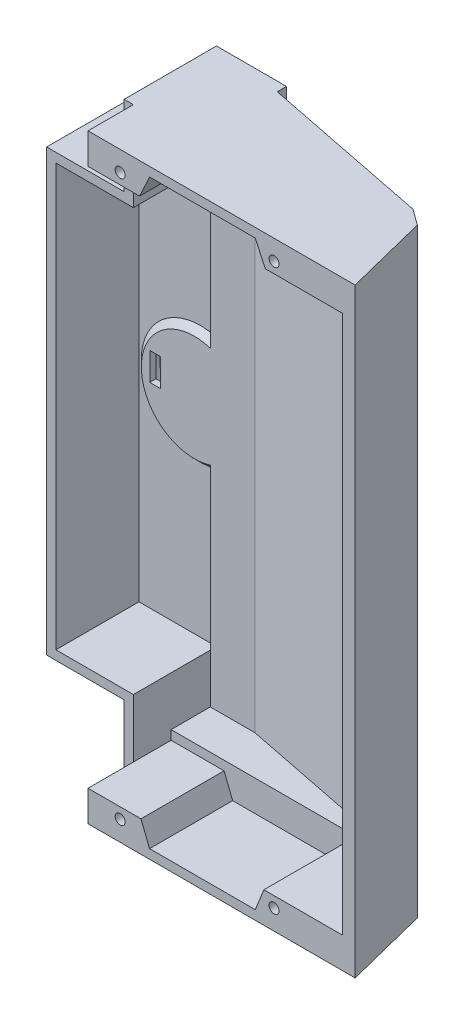
SolidWorks part; units mm, degrees
ref_plane "Alzado" through (0, 0, 0) normal (0, 0, 1) x (1, 0, 0)
ref_plane "Planta" through (0, 0, 0) normal (0, 1, 0) x (1, 0, 0)
ref_plane "Vista lateral" through (0, 0, 0) normal (1, 0, 0) x (0, 0, -1)
sketch "Croquis1" plane through (0, 0, 0) normal (0, 1, 0) x (1, 0, 0)
  line L1 (-39.29, 8.87) -> (39.29, 8.87)
  line L2 (-39.29, 8.87) -> (-39.29, -8.87)
  line L3 (-39.29, -8.87) -> (39.29, -8.87)
  line L4 (39.29, 8.87) -> (39.29, -8.87)
  line L5 (-39.29, 8.87) -> (39.29, -8.87) construction
  line L6 (-39.29, -8.87) -> (39.29, 8.87) construction
  point P0 (0, 0)
  dimension "D1" = 17.74
  dimension "D2" = 78.58
extrude "Saliente-Extruir1" add sketch "Croquis1" along normal blind 195
sketch "Croquis2" plane through (0, 0, 0) normal (0, -1, 0) x (1, 0, 0)
  line L2 (-39.29, 8.87) -> (39.29, 8.87) construction
  line L3 (39.29, 8.87) -> (39.29, -8.87) construction
  line L7 (39.29, 5.87) -> (-19.5325, -5.87)
  line L9 (39.29, -8.87) -> (-39.29, -8.87) construction
  line L10 (-19.5325, -5.87) -> (-19.5325, -8.87)
  line L11 (-19.5325, -8.87) -> (39.29, -8.87)
  line L12 (39.29, -8.87) -> (39.29, 5.87)
  line M3 (39.29, -8.87) -> (39.29, 8.87)
  line M6 (-39.29, -8.87) -> (39.29, -8.87)
  dimension "D1" = 3
  dimension "D2" = 3
extrude "Cortar-Extruir1" cut sketch "Croquis2" against normal through all both and the other way through all contours L7 M3 M6 region at (16.3667, 0, -3.7876)
chamfer "Chaflán1" distance 3 angle 45 1 edges at (39.29, 97.5, 5.87) first distance on face at (39.29, 97.5, 7.37)
sketch "Croquis4" plane through (0, 0, -8.87) normal (0, 0, -1) x (-1, 0, 0)
  line L1 (39.29, 195) -> (42.29, 195)
  line L2 (39.29, 195) -> (39.29, 0)
  line L3 (39.29, 0) -> (42.29, 0)
  line L4 (42.29, 195) -> (42.29, 0)
  dimension "D1" = 3
extrude "Saliente-Extruir2" add sketch "Croquis4" against normal blind 3
sketch "Croquis5" plane through (0, 0, -8.87) normal (0, 0, -1) x (-1, 0, 0)
  line L0 (42.29, 0) -> (42.29, 195) construction
  line L1 (42.29, 26) -> (67.47, 26)
  line L2 (42.29, 26) -> (42.29, 169)
  line L3 (42.29, 169) -> (67.47, 169)
  line L4 (67.47, 26) -> (67.47, 169)
  dimension "D1" = 26
  dimension "D2" = 143
  dimension "D3" = 25.18
extrude "Saliente-Extruir3" add sketch "Croquis5" against normal blind 3
fillet "Redondeo1" radius 2 1 edges at (-67.47, 97.5, -8.87)
sketch "Croquis6" plane through (0, 0, 8.87) normal (0, 0, 1) x (1, 0, 0)
  line L0 (-39.29, 195) -> (-39.29, 0) construction
  line L1 (-39.29, 195) -> (39.29, 195) construction
  line L2 (39.29, 97.5) -> (-154.1795, 97.5) construction
  line L3 (39.29, 195) -> (39.29, 0) construction
  circle A0 centre (-28.84, 188.5) radius 1.625
  circle A1 centre (21.16, 188.5) radius 1.625
  circle A2 centre (21.16, 6.5) radius 1.625
  circle A3 centre (-28.84, 6.5) radius 1.625
  dimension "D2" = 50
  dimension "D3" = 6.5
  dimension "D4" = 3.25
  dimension "D1" = 10.45
extrude "Cortar-Extruir2" cut sketch "Croquis6" against normal through all both and the other way through all
sketch "Croquis7" plane through (0, 0, 8.87) normal (0, 0, 1) x (1, 0, 0)
  circle A0 centre (-28.84, 188.5) radius 3.5
  circle A1 centre (21.16, 188.5) radius 3.5
  circle A2 centre (-28.84, 6.5) radius 3.5
  circle A3 centre (21.16, 6.5) radius 3.5
  dimension "D1" = 7
extrude "Cortar-Extruir3" cut sketch "Croquis7" against normal through all from offset 3 offset against normal yes
sketch "Croquis8" plane through (0, 0, -8.87) normal (0, 0, -1) x (-1, 0, 0)
  line L0 (65.47, 26) -> (65.47, 169) construction
  circle A0 centre (44.4699, 97.5) radius 16.25
  circle A1 centre (44.4699, 97.5) radius 8.75
  point P6 (65.47, 97.5)
  dimension "D1" = 32.5
  dimension "D2" = 17.5
extrude "Cortar-Extruir4" cut sketch "Croquis8" against normal blind 3
sketch "Croquis9" plane through (0, 0, -5.87) normal (0, 0, 1) x (1, 0, 0)
  circle A0 centre (-44.4699, 97.5) radius 17.25
  arc A1 (-39.29, 112.9023) -> (-39.29, 82.0977) centre (-44.4699, 97.5) ccw construction
  dimension "D1" = 1
extrude "Saliente-Extruir4" add sketch "Croquis9" along normal blind 2
chamfer "Chaflán2" distance 2 angle 45 1 edges at (-61.7199, 97.5, -5.87)
sketch "Croquis10" plane through (0, 0, -8.87) normal (0, 0, -1) x (-1, 0, 0)
  line L0 (65.47, 26) -> (65.47, 169) construction
  line L1 (55.47, 103.5) -> (58.97, 103.5)
  line L2 (55.47, 103.5) -> (55.47, 94.5)
  line L3 (55.47, 94.5) -> (58.97, 94.5)
  line L4 (58.97, 103.5) -> (58.97, 94.5)
  point P6 (65.47, 97.5)
  dimension "D1" = 6
  dimension "D2" = 9
  dimension "D3" = 10
  dimension "D4" = 3.5
extrude "Cortar-Extruir6" cut sketch "Croquis10" against normal through all both and the other way through all
sketch "Croquis11" plane through (0.3784, 0, -1.8961) normal (0.1957, 0, -0.9807) x (-0.9807, 0, -0.1957)
  line L0 (-28.8648, 97.5) -> (-15.4588, 92.9473)
  line L1 (-15.4588, 92.9473) -> (-7.5854, 97.5)
  line L2 (-10.6893, 88.7509) -> (-6.961, 83.4264)
  line L3 (-6.961, 83.4264) -> (-14.8132, 81.8958)
  line L4 (-14.8132, 81.8958) -> (-10.6893, 88.7509)
  line L5 (-8.5598, 92.6835) -> (-1.6769, 82.8537)
  line L6 (-1.6769, 82.8537) -> (9.3817, 90.597)
  line L7 (9.3817, 90.597) -> (4.5481, 97.5)
  line L8 (7.0481, 97.5) -> (9.5481, 95)
  line L9 (9.5481, 95) -> (14.0083, 97.5)
  line L10 (-8.5598, 92.6835) -> (-2.4969, 88.3834)
  line L11 (-2.4969, 88.3834) -> (2.418, 91.8249)
  line L12 (2.418, 91.8249) -> (-1.5558, 97.5)
  line L13 (-32.4581, 97.5) -> (-11.1786, 97.5) construction
  line L14 (2.418, 103.1751) -> (-1.5558, 97.5)
  line L15 (-2.4969, 106.6166) -> (2.418, 103.1751)
  line L16 (-8.5598, 102.3165) -> (-2.4969, 106.6166)
  line L17 (9.5481, 100) -> (14.0083, 97.5)
  line L18 (7.0481, 97.5) -> (9.5481, 100)
  line L19 (9.3817, 104.403) -> (4.5481, 97.5)
  line L20 (-1.6769, 112.1463) -> (9.3817, 104.403)
  line L21 (-8.5598, 102.3165) -> (-1.6769, 112.1463)
  line L22 (-14.8132, 113.1042) -> (-10.6893, 106.2491)
  line L23 (-6.961, 111.5736) -> (-14.8132, 113.1042)
  line L24 (-10.6893, 106.2491) -> (-6.961, 111.5736)
  line L25 (-15.4588, 102.0527) -> (-7.5854, 97.5)
  line L26 (-28.8648, 97.5) -> (-15.4588, 102.0527)
  dimension "D1" = 4.5527
  dimension "D2" = 7.8734
  dimension "D3" = 13.4061
  dimension "D4" = 125
  dimension "D5" = 6.5
  dimension "D6" = 8
  dimension "D7" = 1.5
  dimension "D8" = 8
  dimension "D9" = 5
  dimension "D10" = 3.5
  dimension "D11" = 12
  dimension "D12" = 5
  dimension "D13" = 2.5
  dimension "D14" = 10
  dimension "D15" = 2.5
  dimension "D16" = 2.5
  dimension "D17" = 4
  dimension "D18" = 6
extrude "Cortar-Extruir7" cut sketch "Croquis11" against normal blind 1
sketch "Croquis12" plane through (0, 0, 0) normal (0, -1, 0) x (1, 0, 0)
  line L6 (-20.1197, -2.928) -> (-24.8394, -3.87)
  line L8 (-20.1197, -2.928) -> (34.0634, 7.886)
  line L9 (34.0634, 7.886) -> (37.1687, 10.9913)
  line L10 (-20.1197, -2.928) -> (34.0634, 7.886)
  line L11 (34.0634, 7.886) -> (35.0474, 8.87)
  line L12 (-24.8394, -3.87) -> (-39.29, -3.87)
  line L13 (-39.29, -3.87) -> (-61.7199, -3.87) construction
  line L14 (-39.29, -3.87) -> (-39.29, 8.87)
  line L15 (-39.29, 8.87) -> (35.0474, 8.87)
  line L16 (-39.29, 8.87) -> (39.29, 8.87) construction
  dimension "D1" = 3
extrude "Cortar-Extruir8" cut sketch "Croquis12" against normal blind 169 from offset 13 offset against normal yes
sketch "Croquis16" plane through (0, 0, 8.87) normal (0, 0, 1) x (1, 0, 0)
  line L6 (15.05, 3) -> (17.8478, 10)
  line L7 (-39.29, 195) -> (-39.29, 182) construction
  line L10 (-39.29, 195) -> (-19.29, 195)
  line L12 (35.0474, 182) -> (-39.29, 182) construction
  line L15 (35.05, 0) -> (15.05, 0)
  line L19 (-39.29, 195) -> (-39.29, 185)
  line L21 (-39.29, 0) -> (-19.29, 0)
  line L22 (-39.29, 0) -> (-39.29, 10)
  line L26 (35.05, 195) -> (15.05, 195)
  line L27 (35.05, 195) -> (35.05, 185)
  line L30 (-19.29, 0) -> (15.05, 0)
  line L31 (-19.29, 195) -> (15.05, 195)
  line L33 (-19.29, 192) -> (15.05, 192)
  line L36 (-19.29, 3) -> (15.05, 3)
  line L38 (-19.29, 3) -> (-22.086, 10)
  line L39 (35.05, 0) -> (35.05, 10)
  line L40 (35.05, 10) -> (17.8478, 10)
  line L41 (15.05, 192) -> (18.3142, 185)
  line L42 (-19.29, 192) -> (-22.552, 185)
  line L43 (-22.086, 10) -> (-39.29, 10)
  line L44 (-39.29, 185) -> (-22.552, 185)
  line L45 (18.3142, 185) -> (35.05, 185)
  circle A0 centre (-28.84, 6.5) radius 1.625
  circle A1 centre (21.16, 6.5) radius 1.625
  circle A2 centre (-28.84, 188.5) radius 1.625
  circle A3 centre (21.16, 188.5) radius 1.625
  dimension "D3" = 16.738
  dimension "D2" = 10.45
  dimension "D1" = 3.25
  dimension "D4" = 17.204
  dimension "D5" = 20
  dimension "D6" = 54.34
  dimension "D7" = 57.1378
  dimension "D8" = 57.6042
  dimension "D9" = 60.45
  dimension "D10" = 3
  dimension "D11" = 6.5
  dimension "D12" = 10
  dimension "D13" = 13
  dimension "D14" = 172
  dimension "D15" = 175.5
  dimension "D16" = 179
extrude "Saliente-Extruir6" add sketch "Croquis16" along normal blind 27
sketch "Croquis19" plane through (0, 0, -5.87) normal (0, 0, 1) x (1, 0, 0)
  line L2 (-42.29, 26) -> (-42.29, 0)
  line L3 (-42.29, 0) -> (-39.29, 0)
  line L4 (-39.29, 26) -> (-39.29, 0)
  line L11 (-64.47, 29) -> (-39.29, 29)
  line L12 (-39.29, 26) -> (-39.29, 29)
  line L14 (-42.29, 169) -> (-42.29, 195) construction
  line L18 (-64.47, 29) -> (-64.47, 166)
  line L19 (-67.47, 26) -> (-42.29, 26)
  line L23 (-64.47, 166) -> (-39.29, 166)
  line L25 (-39.29, 195) -> (-42.29, 195)
  line L30 (-42.29, 195) -> (-42.29, 169)
  line L32 (-42.29, 169) -> (-67.47, 169)
  line L33 (-67.47, 169) -> (-67.47, 26)
  line L34 (-39.29, 166) -> (-39.29, 195)
  line L36 (-42.29, 195) -> (-39.29, 195) construction
  dimension "D1" = 3
  dimension "D2" = 22.18
  dimension "D3" = 26
  dimension "D4" = 29
  dimension "D5" = 166
extrude "Saliente-Extruir9" add sketch "Croquis19" along normal blind 27
sketch "Croquis20" plane through (0, 0, 0) normal (0, -1, 0) x (1, 0, 0)
  line L0 (47.5106, 35.87) -> (43.3859, 35.87)
  line L1 (-19.5325, -8.87) -> (-19.5325, -5.87) construction
  line L2 (43.3859, 35.87) -> (36.5933, 8.87)
  line L3 (35.05, 8.87) -> (39.29, 8.87) construction
  line L4 (-19.5325, -8.87) -> (-42.29, -8.87) construction
  line L5 (47.5106, 35.87) -> (40.718, 8.87)
  line L6 (40.718, 8.87) -> (35.542, 5.122)
  line L7 (35.542, 5.122) -> (39.29, 8.87) construction
  line L8 (35.542, 5.122) -> (36.5933, 8.87)
  dimension "D1" = 55.0745
  dimension "D2" = 56.1259
  dimension "D3" = 60.2505
  dimension "D4" = 62.9185
  dimension "D5" = 44.74
extrude "Saliente-Extruir10" add sketch "Croquis20" against normal up to vertex (195 mm away) up to point (39.29, 195, 8.87)
sketch "Croquis21" plane through (0, 0, 0) normal (0, -1, 0) x (1, 0, 0)
  line L0 (36.5933, 8.87) -> (35.05, 8.87)
  line L1 (43.3859, 35.87) -> (36.5933, 8.87) construction
  line L2 (35.05, 8.87) -> (35.05, 35.87)
  line L3 (-39.29, 35.87) -> (35.05, 35.87) construction
  line L4 (35.05, 35.87) -> (43.3859, 35.87)
  line L5 (47.5106, 35.87) -> (43.3859, 35.87) construction
  line L6 (43.3859, 35.87) -> (36.5933, 8.87)
  line L7 (35.05, 35.87) -> (35.05, 8.87) construction
  dimension "D1" = 1.5433
extrude "Saliente-Extruir11" add sketch "Croquis21" against normal up to vertex (10 mm away) up to point (35.05, 10, 35.87)
sketch "Croquis22" plane through (0, 195, 0) normal (0, 1, 0) x (1, 0, 0)
  line L0 (35.05, -35.87) -> (43.3859, -35.87)
  line L1 (43.3859, -35.87) -> (17.8478, -35.87) construction
  line L2 (43.3859, -35.87) -> (36.5933, -8.87) construction
  line L3 (43.3859, -35.87) -> (36.5933, -8.87)
  line L4 (36.5933, -8.87) -> (35.05, -8.87)
  line L5 (35.05, -35.87) -> (35.05, -8.87) construction
  line L6 (35.05, -8.87) -> (36.5933, -8.87) construction
  line L7 (35.05, -8.87) -> (35.05, -35.87)
extrude "Saliente-Extruir12" add sketch "Croquis22" against normal up to vertex (10 mm away) up to point (35.05, 185, 35.87)
